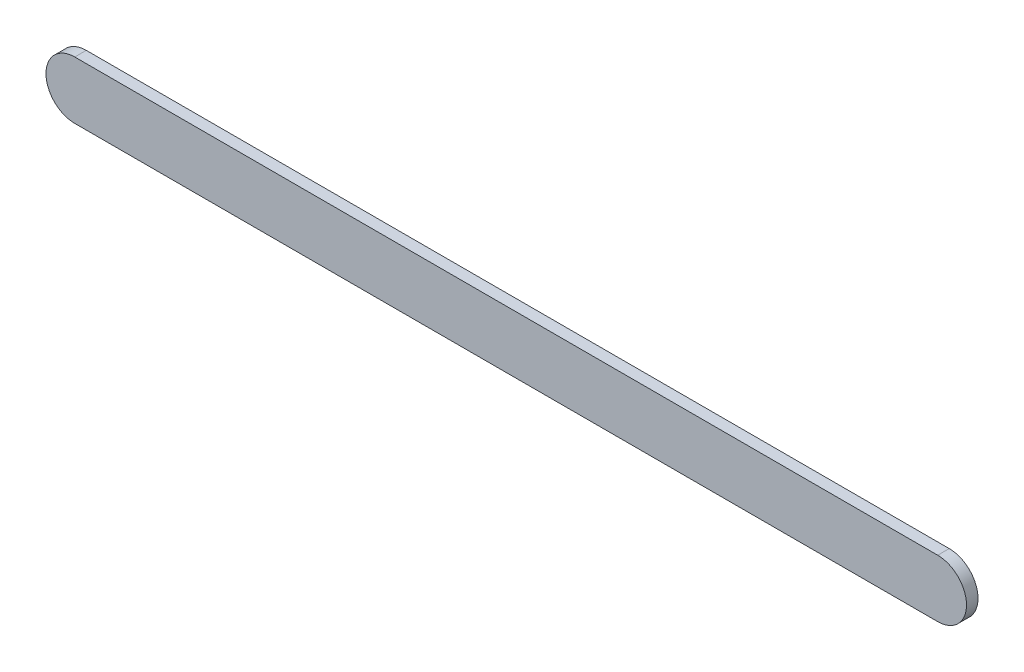
SolidWorks part; units mm, degrees
ref_plane "Front Plane" through (0, 0, 0) normal (0, 0, 1) x (1, 0, 0)
ref_plane "Top Plane" through (0, 0, 0) normal (0, 1, 0) x (1, 0, 0)
ref_plane "Right Plane" through (0, 0, 0) normal (1, 0, 0) x (0, 0, -1)
sketch "Sketch1" plane through (0, 0, 0) normal (0, 0, 1) x (1, 0, 0)
  line L0 (0, 0) -> (150, 0) construction
  line L1 (0, 5) -> (150, 5)
  line L2 (0, -5) -> (150, -5)
  arc A0 (0, 5) -> (0, -5) centre (0, 0) ccw
  arc A1 (150, -5) -> (150, 5) centre (150, 0) ccw
  point P3 (75, 0)
  dimension "D1" = 5
  dimension "D2" = 150
extrude "Boss-Extrude1" add sketch "Sketch1" along normal mid plane 2
